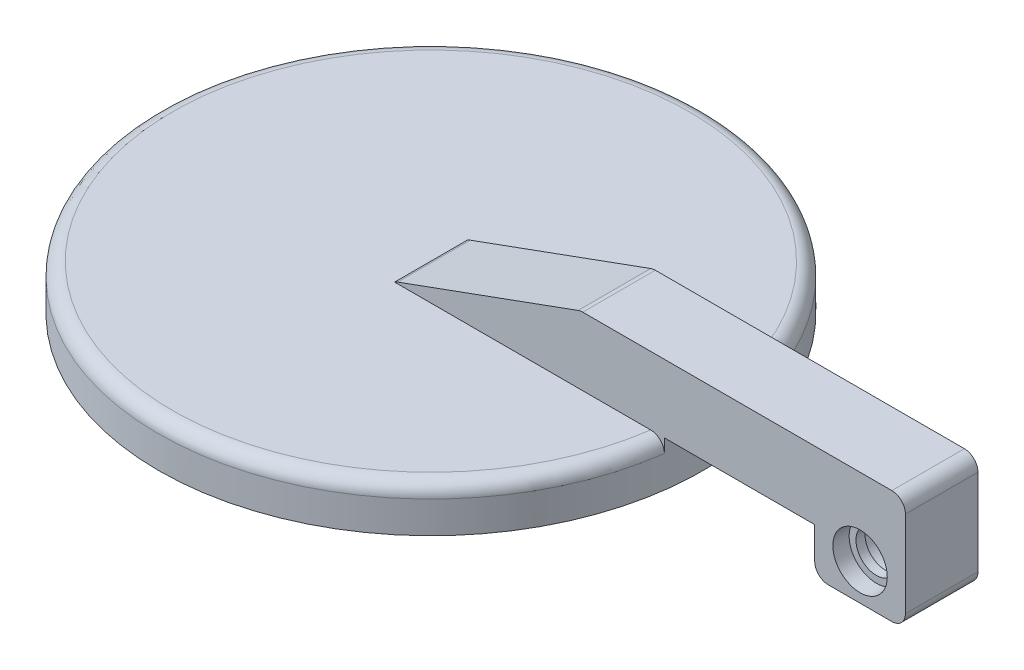
SolidWorks part; units mm, degrees
ref_plane "Front Plane" through (0, 0, 0) normal (0, 0, 1) x (1, 0, 0)
ref_plane "Top Plane" through (0, 0, 0) normal (0, 1, 0) x (1, 0, 0)
ref_plane "Right Plane" through (0, 0, 0) normal (1, 0, 0) x (0, 0, -1)
sketch "Sketch2" plane through (0, 0, 0) normal (0, 0, 1) x (1, 0, 0)
  line L7 (0, 0) -> (30, 0)
  line L8 (0, 0) -> (0, 5)
  line L9 (0, 5) -> (30, 5)
  line L10 (30, 0) -> (30, 5)
  dimension "D1" = 5
  dimension "D2" = 30
revolve "Revolve1" add sketch "Sketch2" angle 360 about L8
sketch "Sketch3" plane through (0, 5, 0) normal (0, 1, 0) x (1, 0, 0)
  line L0 (0, -10) -> (0, 10) construction
  line L1 (0, 10) -> (35, 10)
  line L2 (35, 10) -> (35, 6)
  line L3 (35, 6) -> (0, 6)
  line L4 (0, 10) -> (0, 6)
  line L5 (0, -10) -> (35, -10)
  line L6 (35, -10) -> (35, -6)
  line L7 (35, -6) -> (0, -6)
  line L8 (0, -6) -> (0, -10)
  line L9 (0, 4) -> (0, -4)
  line L10 (0, 4) -> (56.3, 4)
  line L11 (0, -4) -> (56.3, -4)
  line L12 (56.3, -4) -> (56.3, 4)
  point P4 (0, 0)
  point P13 (0, 0)
  circle M1 centre (0, 0) radius 30
  dimension "D1" = 20
  dimension "D2" = 35
  dimension "D3" = 4
  dimension "0.7" = 8
  dimension "D5" = 56.3
extrude "Boss-Extrude1" add sketch "Sketch3" along normal blind 7.5 contours L9 L11 L10 M1 | L11 L12 L10 M1 region at (14.9555, 5, 0) region at (43.1053, 5, 0)
sketch "Sketch4" plane through (0, 0, 0) normal (0, 0, 1) x (1, 0, 0)
  line L5 (35, 8.75) -> (37.8, 8.75) construction
  line L7 (56.3, 8.75) -> (37.8, 8.75) construction
  line L8 (56.3, 12.5) -> (56.3, 5) construction
  line L10 (-0.1339, 5) -> (20.4721, 12.5)
  line L11 (29.7321, 5) -> (-30, 5) construction
  line L12 (0, 12.5) -> (56.3, 12.5) construction
  line L13 (0, 5) -> (29.7321, 5) construction
  line L14 (20.4721, 12.5) -> (0, 12.5)
  line L15 (0, 12.5) -> (-0.1339, 5)
  circle A0 centre (37.8, 8.75) radius 2
  dimension "D3" = 4
  dimension "D1" = 20
  dimension "D2" = 18.5
extrude "Cut-Extrude1" cut sketch "Sketch4" against normal mid plane 30 contours L14 L15 L10
sketch "Sketch6" plane through (0, 5, 0) normal (0, -1, 0) x (1, 0, 0)
  line L6 (56.3, 4) -> (46.3, 4)
  line L7 (56.3, 4) -> (56.3, -4) construction
  line L8 (29.7321, 4) -> (56.3, 4) construction
  line L9 (46.3, 4) -> (46.3, -4)
  line L10 (29.7321, -4) -> (56.3, -4) construction
  line L11 (46.3, -4) -> (56.3, -4)
  line L12 (56.3, -4) -> (56.3, 4)
  dimension "D1" = 10
extrude "Boss-Extrude2" add sketch "Sketch6" along normal blind 5
sketch "Sketch7" plane through (0, 0, 4) normal (0, 0, 1) x (1, 0, 0)
  line L0 (51.3, 4) -> (51.3, 0) construction
  line L2 (56.3, 0) -> (46.3, 0) construction
  circle A0 centre (51.3, 4) radius 3
  dimension "D2" = 6
  dimension "D1" = 4
extrude "Cut-Extrude2" cut sketch "Sketch7" against normal blind 10
fillet "Fillet2" radius 1.5 6 edges at (46.3, 0, 0) (56.3, 0, 0) (56.3, 12.5, 0) (20.4721, 12.5, 0) (0, 5.0487, 0) (-30, 5, 0)
sketch "Sketch9" plane through (0, 0, -4) normal (0, 0, -1) x (-1, 0, 0)
  circle A0 centre (-51.3, 4) radius 3
  circle A1 centre (-51.3, 4) radius 4
  dimension "D1" = 6
  dimension "D2" = 8
sketch "Sketch10" plane through (0, 0, 4) normal (0, 0, 1) x (1, 0, 0)
  circle A0 centre (51.3, 4) radius 3
  circle A1 centre (51.3, 4) radius 2.25
  dimension "D1" = 6
  dimension "D2" = 4.5
extrude "Boss-Extrude4" add sketch "Sketch10" along normal blind 1 from offset 2.8 offset against normal yes
sketch "Sketch11" plane through (0, 0, 1.2) normal (0, 0, -1) x (-1, 0, 0)
  circle A0 centre (-51.3, 4) radius 2.6
  circle A1 centre (-51.3, 4) radius 3
  dimension "D1" = 5.2
extrude "Boss-Extrude5" add sketch "Sketch11" along normal blind 5.2
sketch "Sketch12" plane through (0, 0, 0) normal (0, -1, 0) x (1, 0, 0)
  line L0 (0, 30) -> (0, 25.5) construction
  circle A0 centre (0, 0) radius 30 construction
  circle A1 centre (0, 27.75) radius 1
  circle A2 centre (19.6222, 19.6222) radius 1
  circle A3 centre (27.75, 0) radius 1
  circle A4 centre (19.6222, -19.6222) radius 1
  circle A5 centre (0, -27.75) radius 1
  circle A6 centre (-19.6222, -19.6222) radius 1
  circle A7 centre (-27.75, 0) radius 1
  circle A8 centre (-19.6222, 19.6222) radius 1
  point P24 (0, 0)
  dimension "D2" = 2
  dimension "D1" = 4.5
  dimension "D3" = 8
extrude "Cut-Extrude3" cut sketch "Sketch12" against normal blind 0.3
